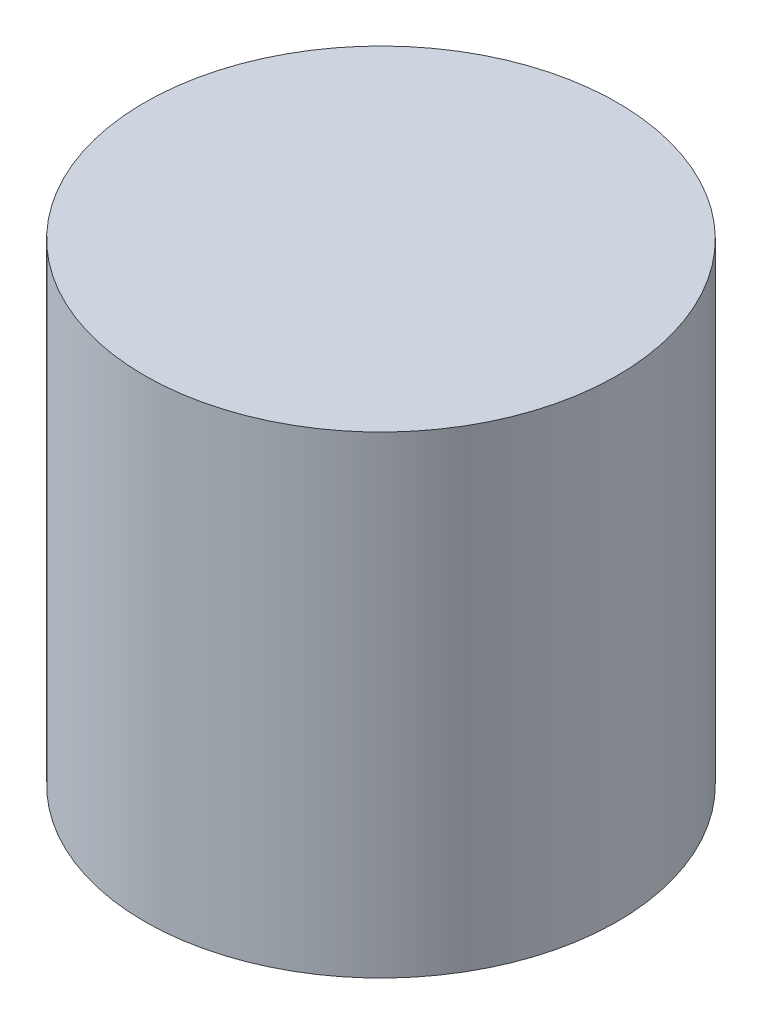
SolidWorks part; units mm, degrees
ref_plane "Front Plane" through (0, 0, 0) normal (0, 0, 1) x (1, 0, 0)
ref_plane "Top Plane" through (0, 0, 0) normal (0, 1, 0) x (1, 0, 0)
ref_plane "Right Plane" through (0, 0, 0) normal (1, 0, 0) x (0, 0, -1)
sketch "Sketch1" plane through (0, 0, 0) normal (0, 1, 0) x (1, 0, 0)
  circle A0 centre (0, 0) radius 15.875
  circle A1 centre (0, 0) radius 12.7
  dimension "D1" = 25.4
  dimension "D2" = 3.175
extrude "Boss-Extrude1" add sketch "Sketch1" along normal blind 25.4
sketch "Sketch4" plane through (0, 25.4, 0) normal (0, 1, 0) x (1, 0, 0)
  circle A0 centre (0, 0) radius 15.875
  circle A1 centre (0, 0) radius 12.7 construction
  dimension "D1" = 3.175
extrude "Boss-Extrude2" add sketch "Sketch4" along normal blind 6.35
sketch "Sketch5" plane through (0, 31.75, 0) normal (0, 1, 0) x (1, 0, 0)
  circle A0 centre (0, 0) radius 6.35
  dimension "D1" = 12.7
equation "\"Pstrut_L\"= 36in"
equation "\"Pstrut_D\"= 1in"
equation "\"Pstrut_T\"= 0.25"
equation "\"Sstrut_L\"= 36in"
equation "\"Sstrut_D\"= 0.5in"
equation "\"Sstrut_T\"= 0.125"
equation "\"Dstrut_L\"= 10in"
equation "\"Dstrut_D\"= 0.5in"
equation "\"Dstrut_T\"= 0.125"
equation "\"D1@Sketch1\"=\"Pstrut_D\""
equation "\"D1@Boss-Extrude2\"=\"Pstrut_T\""
